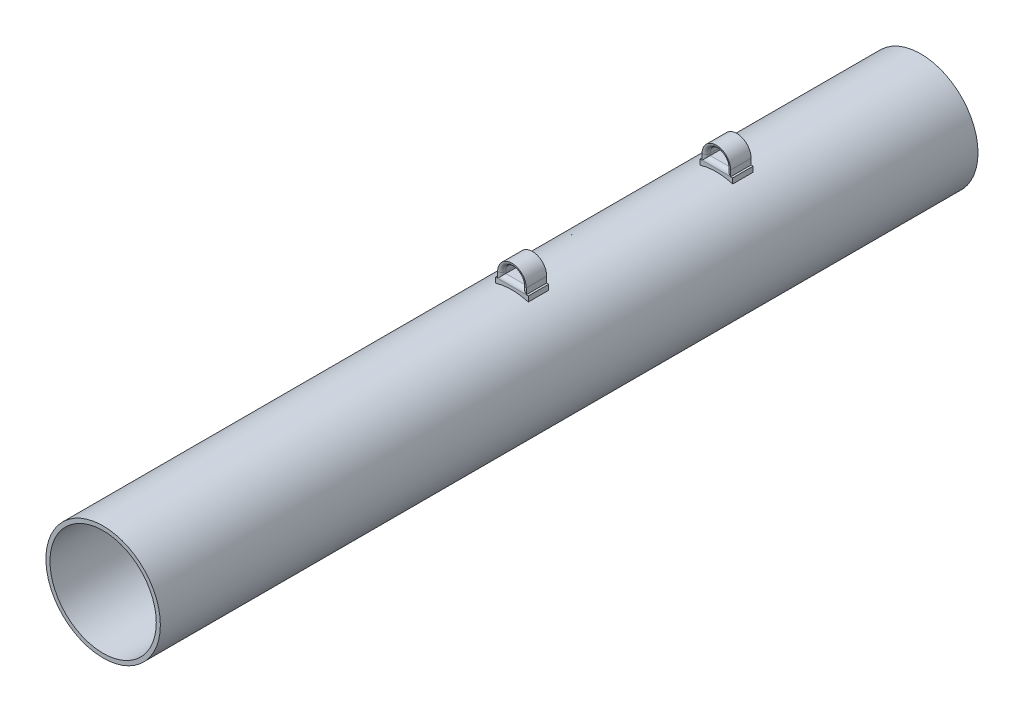
SolidWorks part; units mm, degrees
ref_plane "Alzado" through (0, 0, 0) normal (0, 0, 1) x (1, 0, 0)
ref_plane "Planta" through (0, 0, 0) normal (0, 1, 0) x (1, 0, 0)
ref_plane "Vista lateral" through (0, 0, 0) normal (1, 0, 0) x (0, 0, -1)
sketch "Croquis1" plane through (0, 0, 0) normal (0, 0, 1) x (1, 0, 0)
  circle A0 centre (0, 0) radius 14
  dimension "D1" = 28
extrude "Saliente-Extruir1" add sketch "Croquis1" against normal blind 200
sketch "Croquis2" plane through (0, 0, 0) normal (0, 0, 1) x (1, 0, 0)
  circle A0 centre (0, 0) radius 13
  dimension "D1" = 26
extrude "Cortar-Extruir1" cut sketch "Croquis2" against normal through all both and the other way through all
ref_plane "Plano1" through (0, 0, -100) normal (0, 0, 1) x (1, 0, 0)
sketch "Croquis3" plane through (0, 0, -100) normal (0, 0, 1) x (1, 0, 0)
  line L0 (0, 0) -> (0, 14) construction
  line L2 (-4, 13.3) -> (4, 13.3)
  line L3 (-4, 13.3) -> (-4, 14.7)
  line L4 (-4, 14.7) -> (4, 14.7)
  line L5 (4, 13.3) -> (4, 14.7)
  line L6 (-4, 13.3) -> (4, 14.7) construction
  line L7 (-4, 14.7) -> (4, 13.3) construction
  circle A1 centre (0, 0) radius 14 construction
  dimension "D1" = 8
  dimension "D2" = 1.4
extrude "Saliente-Extruir2" add sketch "Croquis3" against normal blind 5
sketch "Croquis5" plane through (0, 0, -100) normal (0, 0, 1) x (1, 0, 0)
  line L0 (-2.5, 14.7) -> (2.5, 14.7)
  line L1 (4, 14.7) -> (-4, 14.7) construction
  line L2 (-2.5, 14.7) -> (-2.5, 15.7)
  line L4 (-2.5, 15.7) -> (-2.5, 16.1421)
  line L6 (2.5, 16.1421) -> (2.5, 14.7)
  arc A1 (2.5, 16.1421) -> (-2.5, 16.1421) centre (0, 16.1421) ccw
  point P5 (0, 14.7)
  dimension "D1" = 5
  dimension "D2" = 1
extrude "Extruir-Lámina2" add sketch "Croquis5" against normal up to surface (5 mm away) thin up to face at (0, 14.2041, -105) thin type one direction wall 1
sketch "Croquis6" plane through (0, 14.7, 0) normal (0, 1, 0) x (1, 0, 0)
  line L4 (2.5, 105) -> (-2.5, 105)
  line L5 (-2.5, 105) -> (-2.5, 100)
  line L6 (-2.5, 100) -> (2.5, 100)
  line L8 (2.5, 105) -> (-2.5, 105)
  line L10 (-2.5, 100) -> (2.5, 100)
  line L12 (-2.5, 105) -> (-2.5, 100)
  line L14 (2.5, 100) -> (2.5, 105)
  line L15 (2.5, 100) -> (2.5, 105)
  dimension "D1" = 0
extrude "Saliente-Extruir3" add sketch "Croquis6" along normal blind 1
fillet "Redondeo1" radius 1 8 edges at (2.5, 15.9211, -105) (-2.5, 15.9211, -105) (2.5, 15.9211, -100) (-2.5, 15.9211, -100) (0, 15.7, -105) (0, 18.6421, -105) (0, 15.7, -100) (0, 18.6421, -100)
pattern_linear "MatrizL2" count 2 spacing 50 along (0, 0, -1) of "Saliente-Extruir2", "Extruir-Lámina2", "Saliente-Extruir3", "Redondeo1"
sketch "Croquis8" plane through (0, 0, -200) normal (0, 0, -1) x (-1, 0, 0)
  circle A0 centre (0, 0) radius 13.5
  dimension "D1" = 27
extrude "Cortar-Extruir2" cut sketch "Croquis8" against normal blind 50
